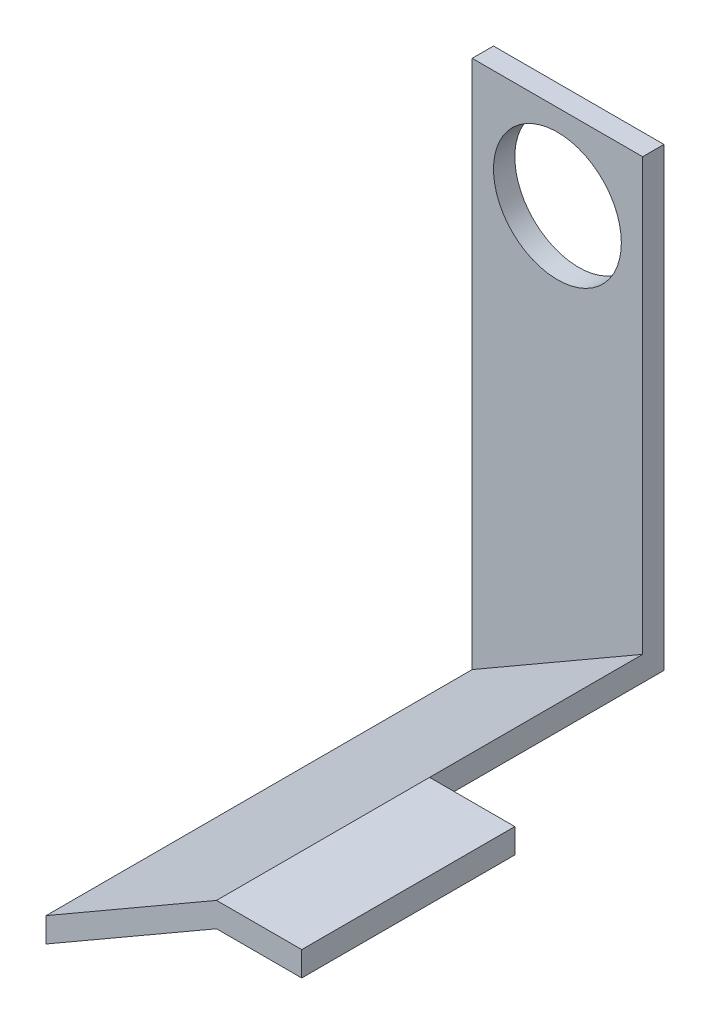
SolidWorks part; units mm, degrees
ref_plane "Front" through (0, 0, 0) normal (0, 0, 1) x (1, 0, 0)
ref_plane "Top" through (0, 0, 0) normal (0, 1, 0) x (1, 0, 0)
ref_plane "Right" through (0, 0, 0) normal (1, 0, 0) x (0, 0, -1)
sketch "Эскиз4" plane through (0, 0, 0) normal (0, 0, 1) x (1, 0, 0)
  line L0 (-2, -7) -> (2, -4.6906)
  line L2 (-2, -7) -> (-2, 6)
  line L3 (-2, 6) -> (2, 6)
  line L4 (2, -4.6906) -> (2, 6)
  circle A0 centre (0, 4) radius 1.5
  point P0 (0, 0)
  dimension "D1" = 4
  dimension "D2" = 2
  dimension "D4" = 13
  dimension "D5" = 60
extrude "Бобышка-Вытянуть3" add sketch "Эскиз4" along normal blind 0.5
sketch "Эскиз5" plane through (0, 0, 0.5) normal (0, 0, 1) x (1, 0, 0)
  line L0 (-2, -7) -> (2, -4.6906)
  line L1 (2, -4.6906) -> (2, -4.1132)
  line L3 (2, -4.1132) -> (-2, -6.4226)
  line L4 (-2, 6) -> (-2, -7) construction
  line L5 (-2, -6.4226) -> (-2, -7)
  line L6 (2, -4.6906) -> (2, 6) construction
  dimension "D1" = 0.5
extrude "Бобышка-Вытянуть4" add sketch "Эскиз5" along normal blind 10
sketch "Эскиз6" plane through (2, 0, 0) normal (1, 0, 0) x (0, 0, -1)
  line L0 (-10.5, -4.6906) -> (0, -4.6906) construction
  line L1 (-10.5, -4.1132) -> (-5.5, -4.1132)
  line L2 (-10.5, -4.1132) -> (-10.5, -4.6906)
  line L3 (-10.5, -4.6906) -> (-5.5, -4.6906)
  line L4 (-5.5, -4.1132) -> (-5.5, -4.6906)
  dimension "D1" = 5
extrude "Бобышка-Вытянуть5" add sketch "Эскиз6" along normal blind 2
